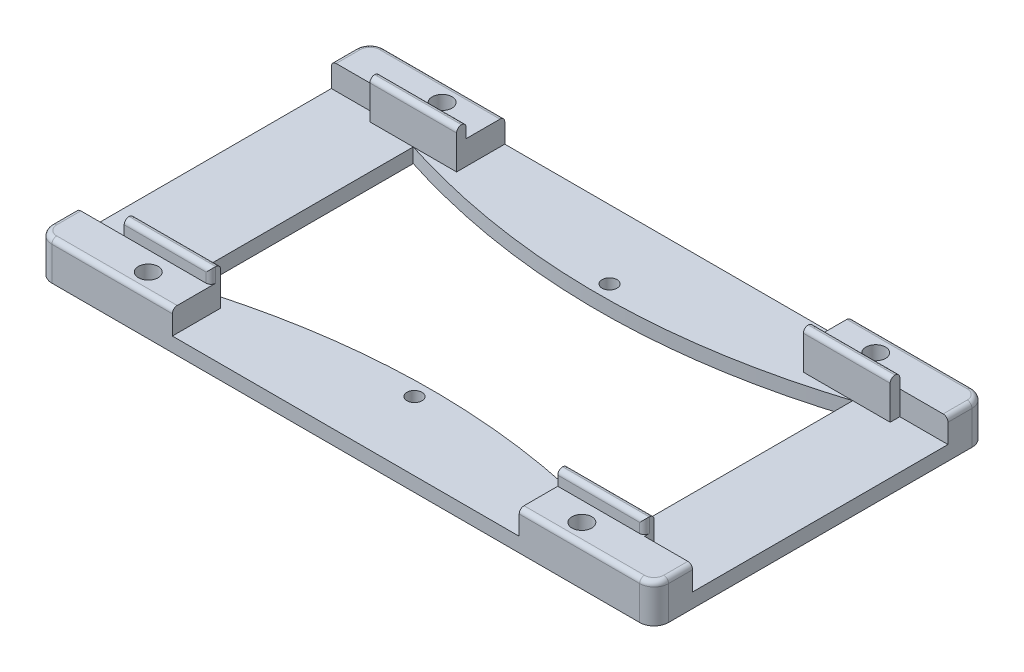
SolidWorks part; units mm, degrees
material "ABS"
ref_plane "Front Plane" through (0, 0, 0) normal (0, 0, 1) x (1, 0, 0)
ref_plane "Top Plane" through (0, 0, 0) normal (0, 1, 0) x (1, 0, 0)
ref_plane "Right Plane" through (0, 0, 0) normal (1, 0, 0) x (0, 0, -1)
sketch "Sketch1" plane through (0, 0, 0) normal (0, 1, 0) x (1, 0, 0)
  line L1 (-64, -34.5) -> (64, -34.5)
  line L2 (-64, -34.5) -> (-64, 34.5)
  line L3 (-64, 34.5) -> (64, 34.5)
  line L4 (64, -34.5) -> (64, 34.5)
  line L5 (-64, -34.5) -> (64, 34.5) construction
  line L6 (-64, 34.5) -> (64, -34.5) construction
  point P0 (0, 0)
  dimension "D1" = 128
  dimension "D2" = 69
extrude "Boss-Extrude1" add sketch "Sketch1" along normal blind 3
sketch "Sketch2" plane through (0, 3, 0) normal (0, 1, 0) x (1, 0, 0)
  line L0 (0, 30.5) -> (0, -30.5) construction
  line L1 (-45, -30.5) -> (45, -30.5) construction
  line L2 (-45, -30.5) -> (-45, 30.5) construction
  line L3 (-45, 30.5) -> (45, 30.5) construction
  line L4 (45, -30.5) -> (45, 30.5) construction
  line L5 (-45, -30.5) -> (45, 30.5) construction
  line L6 (-45, 30.5) -> (45, -30.5) construction
  circle A0 centre (-45, 30.5) radius 2.05
  circle A2 centre (45, 30.5) radius 2.05
  circle A3 centre (45, -30.5) radius 2.05
  circle A5 centre (-45, -30.5) radius 2.05
  point P0 (0, 0)
  dimension "D3" = 4.1
  dimension "D4" = 4.1
  dimension "D5" = 4.1
  dimension "D1" = 90
  dimension "D2" = 61
ref_point "Point1"
sketch "Sketch5" plane through (0, 3, 0) normal (0, 1, 0) x (1, 0, 0)
  line L1 (64, 34.5) -> (-64, 34.5) construction
  line L2 (20, 30) -> (20, -34.5)
  line L3 (-64, -34.5) -> (64, -34.5) construction
  line L4 (20, -34.5) -> (-20, -34.5)
  line L5 (-20, -34.5) -> (-20, 34.5)
  line L6 (-20, 34.5) -> (20, 34.5)
  line L7 (20, 34.5) -> (20, 30)
  line L8 (0, -20.25) -> (0, 20.25) construction
  circle A2 centre (0, -20.25) radius 1.55
  circle A3 centre (0, 20.25) radius 1.55
  point P4 (0, 30)
  point P17 (0, 0)
  dimension "D2" = 3.1
  dimension "D3" = 3.1
  dimension "D4" = 40.5
extrude "Cut-Extrude5" cut sketch "Sketch5" against normal blind 10 contours A3 | A2 region at (0, 3, -20.25)
sketch "Sketch7" plane through (0, 3, 0) normal (0, 1, 0) x (1, 0, 0)
  line L0 (-64, 34.5) -> (-64, -34.5) construction
  line L1 (-64, 34.5) -> (-36, 34.5)
  line L2 (-64, 34.5) -> (-64, 26.5)
  line L3 (-64, 26.5) -> (-36, 26.5)
  line L4 (-36, 34.5) -> (-36, 26.5)
  line L5 (64, 34.5) -> (-64, 34.5) construction
  line L6 (0, 0) -> (61.5399, 0) construction
  line L7 (0, 0) -> (0, 61.3572) construction
  line L8 (36, 34.5) -> (36, 26.5)
  line L9 (64, 26.5) -> (36, 26.5)
  line L10 (64, 34.5) -> (64, 26.5)
  line L11 (64, 34.5) -> (36, 34.5)
  line L12 (64, -34.5) -> (36, -34.5)
  line L13 (64, -34.5) -> (64, -26.5)
  line L14 (64, -26.5) -> (36, -26.5)
  line L15 (36, -34.5) -> (36, -26.5)
  line L16 (-36, -34.5) -> (-36, -26.5)
  line L17 (-64, -26.5) -> (-36, -26.5)
  line L18 (-64, -34.5) -> (-64, -26.5)
  line L19 (-64, -34.5) -> (-36, -34.5)
  dimension "D1" = 28
  dimension "D2" = 8
extrude "Boss-Extrude2" add sketch "Sketch7" along normal blind 5
extrude "Cut-Extrude6" cut sketch "Sketch2" against normal through all and the other way up to next
ref_plane "Plane1" through (0, 0, 0) normal (0, 0, -1) x (-1, 0, 0)
sketch "Sketch6" plane through (0, 3, 0) normal (0, 1, 0) x (1, 0, 0)
  line L0 (-45, 30.5) -> (-45, 24.5) construction
  line L1 (0, 20.25) -> (0, 17.25) construction
  line L2 (1.65, 0) -> (-1.65, 0) construction
  line L3 (-45, 24.5) -> (-45, -24.5)
  line L4 (46.2411, 24.5) -> (46.2411, -24.5)
  circle A3 centre (45, 30.5) radius 2.05 construction
  spline S0 degree 2 poles (-45, 24.5) (0.59, 9.9974) (46.2411, 24.5) knots 0 0 0 1 1 1
  spline S1 degree 2 poles (-45, -24.5) (0.59, -9.9974) (46.2411, -24.5) knots 0 0 0 1 1 1
  dimension "D4" = 92.7554
  dimension "D1" = 6
  dimension "D2" = 3
  dimension "D3" = 6
extrude "Cut-Extrude7" cut sketch "Sketch6" against normal up to surface (3 mm away) up to face at (-45, 0, 32.55)
sketch "Sketch8" plane through (0, 3, 0) normal (0, 1, 0) x (1, 0, 0)
  line L0 (-36, 26.5) -> (-36, 34.5) construction
  line L1 (-54, 26.5) -> (-36, 26.5)
  line L2 (-54, 26.5) -> (-54, 24.5)
  line L3 (-54, 24.5) -> (-36, 24.5)
  line L4 (-36, 26.5) -> (-36, 24.5)
  line L5 (1.65, 0) -> (-1.65, 0) construction
  line L6 (-36, -26.5) -> (-36, -24.5)
  line L7 (-54, -24.5) -> (-36, -24.5)
  line L8 (-54, -26.5) -> (-54, -24.5)
  line L9 (-54, -26.5) -> (-36, -26.5)
  line L10 (0, -49.4012) -> (0, 49.4012) construction
  line L11 (54, -26.5) -> (36, -26.5)
  line L12 (54, -26.5) -> (54, -24.5)
  line L13 (54, -24.5) -> (36, -24.5)
  line L14 (36, -26.5) -> (36, -24.5)
  line L15 (36, 26.5) -> (36, 24.5)
  line L16 (54, 24.5) -> (36, 24.5)
  line L17 (54, 26.5) -> (54, 24.5)
  line L18 (54, 26.5) -> (36, 26.5)
  line L19 (-64, 26.5) -> (-36, 26.5) construction
  point P18 (0, 0)
  dimension "D1" = 2
  dimension "D2" = 18
extrude "Boss-Extrude3" add sketch "Sketch8" along normal blind 8
fillet "Fillet1" radius 3 4 edges at (-64, 4, -34.5) (64, 4, -34.5) (64, 4, 34.5) (-64, 4, 34.5)
fillet "Fillet2" radius 1 23 edges at (64, 8, -29) (63.1213, 8, -33.6213) (48.5, 8, -34.5) (36, 5.5, -34.5) (45, 11, -24.5) (45, 11, -26.5) (45, 11, 26.5) (45, 11, 24.5) (-45, 11, 26.5) (-45, 11, 24.5) (-45, 11, -24.5) (-45, 11, -26.5) (-64, 8, -29) (-63.1213, 8, -33.6213) (-64, 8, 29) (-63.1213, 8, 33.6213) (48.5, 8, 34.5) (63.1213, 8, 33.6213) (-48.5, 8, -34.5) (-48.5, 8, 34.5) (-36, 9.5, 26.5) (54, 9.5, 26.5) (64, 8, 29)
